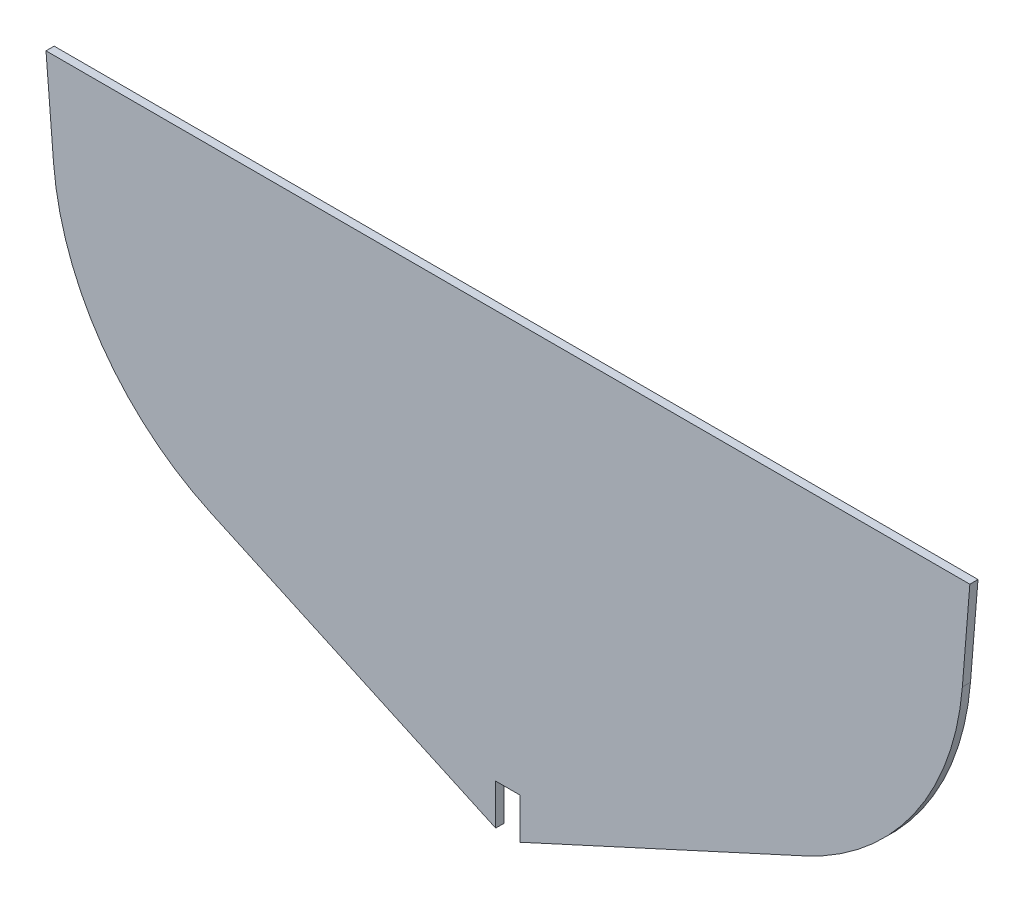
SolidWorks part; units mm, degrees
ref_plane "Plan de face" through (0, 0, 0) normal (0, 0, 1) x (1, 0, 0)
ref_plane "Plan de dessus" through (0, 0, 0) normal (0, 1, 0) x (1, 0, 0)
ref_plane "Plan de droite" through (0, 0, 0) normal (1, 0, 0) x (0, 0, -1)
sketch "Esquisse1" plane through (0, 0, 0) normal (0, 0, 1) x (1, 0, 0)
  line L0 (-133.9234, 132.6316) -> (206.0766, 132.6316)
  line L1 (-133.9234, 132.6316) -> (-126.4395, 40.0765)
  line L2 (-126.4395, 40.0765) -> (31.5766, -32.3684)
  line L3 (31.5766, -32.3684) -> (31.5766, -17.3684)
  line L4 (31.5766, -17.3684) -> (40.5766, -17.3684)
  line L5 (36.0766, 132.6316) -> (36.0766, -17.3684) construction
  line L6 (40.5766, -32.3684) -> (40.5766, -17.3684)
  line L7 (198.5926, 40.0765) -> (40.5766, -32.3684)
  line L8 (206.0766, 132.6316) -> (198.5926, 40.0765)
  point P10 (278.5926, 40.0765)
  dimension "D1" = 170
  dimension "D4" = 9
  dimension "D5" = 15
  dimension "D6" = 150
extrude "Boss.-Extru.1" add sketch "Esquisse1" along normal blind 3
fillet "Congé1" radius 100 2 edges at (-126.4395, 40.0765, 1.5) (198.5926, 40.0765, 1.5)
